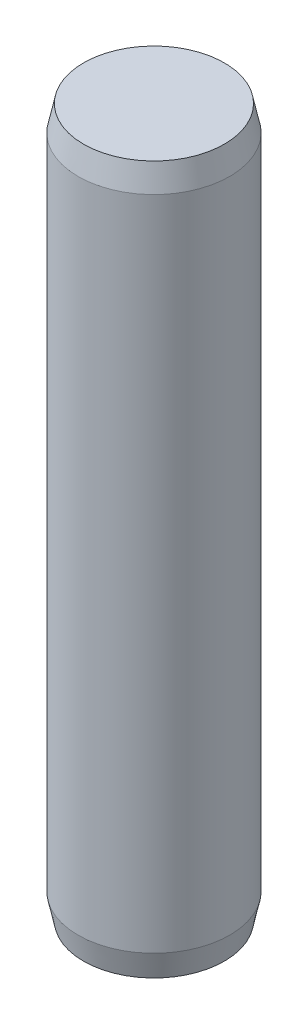
SolidWorks part; units mm, degrees
ref_plane "Front Plane" through (0, 0, 0) normal (0, 0, 1) x (1, 0, 0)
ref_plane "Top Plane" through (0, 0, 0) normal (0, 1, 0) x (1, 0, 0)
ref_plane "Right Plane" through (0, 0, 0) normal (1, 0, 0) x (0, 0, -1)
sketch "Sketch1" plane through (0, 0, 0) normal (0, 1, 0) x (1, 0, 0)
  circle A0 centre (0, 0) radius 1.5
  dimension "D1" = 3
extrude "Boss-Extrude1" add sketch "Sketch1" along normal blind 14
chamfer "Chamfer1" distance 0.5 angle 12 1 edges at (0, 14, 1.5) first distance on face at (0, 14, 1.5)
chamfer "Chamfer2" distance 0.5 angle 12 1 edges at (0, 0, 1.5) first distance on face at (0, 13.5, 1.5)
